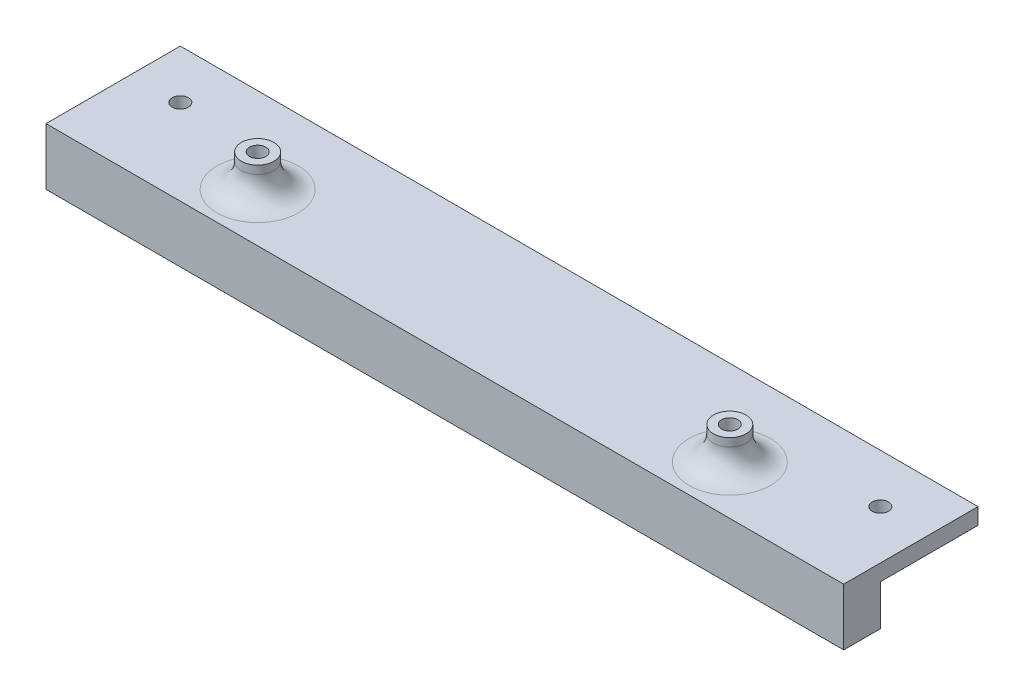
SolidWorks part; units mm, degrees
ref_plane "前视基准面" through (0, 0, 0) normal (0, 0, 1) x (1, 0, 0)
ref_plane "上视基准面" through (0, 0, 0) normal (0, 1, 0) x (1, 0, 0)
ref_plane "右视基准面" through (0, 0, 0) normal (1, 0, 0) x (0, 0, -1)
sketch "草图1" plane through (0, 0, 0) normal (0, 1, 0) x (1, 0, 0)
  line L0 (130, 16.5685) -> (106.5685, 40) construction
  line L2 (16.5685, 40) -> (-16.5685, 40) construction
  line L3 (-16.5685, 40) -> (-40, 16.5685) construction
  line L4 (-40, 16.5685) -> (-40, -16.5685) construction
  line L5 (-40, -16.5685) -> (-16.5685, -40) construction
  line L6 (-16.5685, -40) -> (16.5685, -40) construction
  line L9 (106.5685, 40) -> (73.4315, 40) construction
  line L13 (73.4315, -40) -> (106.5685, -40) construction
  line L14 (106.5685, -40) -> (130, -16.5685) construction
  line L15 (130, -16.5685) -> (130, 16.5685) construction
  line L16 (0, 0) -> (90, 0) construction
  line L17 (16.5685, 40) -> (73.4315, 40) construction
  line L18 (16.5685, -40) -> (73.4315, -40) construction
  line L19 (16.5685, 42.5) -> (73.4315, 42.5)
  line L20 (16.5685, 42.5) -> (-17.6041, 42.5)
  line L21 (-17.6041, 42.5) -> (-42.5, 17.6041)
  line L22 (-42.5, 17.6041) -> (-42.5, -17.6041)
  line L23 (-42.5, -17.6041) -> (-17.6041, -42.5)
  line L24 (-17.6041, -42.5) -> (16.5685, -42.5)
  line L25 (73.4315, -42.5) -> (107.6041, -42.5)
  line L26 (107.6041, -42.5) -> (132.5, -17.6041)
  line L27 (132.5, -17.6041) -> (132.5, 17.6041)
  line L28 (132.5, 17.6041) -> (107.6041, 42.5)
  line L29 (107.6041, 42.5) -> (73.4315, 42.5)
  line L30 (16.5685, -42.5) -> (73.4315, -42.5)
  line L31 (28.2843, 28.2843) -> (16.5685, 40)
  line L32 (40, -16.5685) -> (40, 0)
  line L33 (16.5685, -40) -> (28.2843, -28.2843)
  line L34 (16.5685, 37.5) -> (-15.533, 37.5)
  line L41 (-15.533, 37.5) -> (-37.5, 15.533)
  line L42 (-37.5, 15.533) -> (-37.5, -15.533)
  line L43 (-37.5, -15.533) -> (-15.533, -37.5)
  line L44 (-15.533, -37.5) -> (-7.5, -37.5)
  line L45 (16.5685, -37.5) -> (73.4315, -37.5)
  line L46 (73.4315, -37.5) -> (83.1419, -37.5)
  line L47 (105.533, -37.5) -> (127.5, -15.533)
  line L48 (127.5, -15.533) -> (127.5, 15.533)
  line L49 (127.5, 15.533) -> (105.533, 37.5)
  line L50 (105.533, 37.5) -> (73.4315, 37.5)
  line L51 (16.5685, 37.5) -> (73.4315, 37.5)
  line L52 (-7.5, 24) -> (-29.033, 24)
  line L53 (-1, -36) -> (91, -36) construction
  line L54 (-1, -28) -> (-1, 16) construction
  line L55 (7, 24) -> (83, 24)
  line L56 (91, -28) -> (91, 16) construction
  line L57 (-1, -36) -> (91, 24) construction
  line L58 (-1, 24) -> (91, -36) construction
  line L59 (97.5, 24) -> (119.033, 24)
  line L60 (-7.5, 24) -> (-7.5, -37.5)
  line L61 (91, 16) -> (91, -28)
  line L62 (6.8581, -37.5) -> (16.5685, -37.5)
  line L63 (-15.533, -37.5) -> (16.5685, -37.5) construction
  line L64 (-1, -28) -> (-1, 16)
  line L65 (97.5, 24) -> (97.5, -37.5)
  line L66 (97.5, -37.5) -> (105.533, -37.5)
  line L67 (73.4315, -37.5) -> (105.533, -37.5) construction
  arc A0 (0, 40) -> (0, -40) centre (0, 0) ccw construction
  arc A1 (90, -40) -> (90, 40) centre (90, 0) ccw construction
  arc A2 (-1, 16) -> (7, 24) centre (-1, 24) ccw
  arc A3 (83, 24) -> (91, 16) centre (91, 24) ccw
  arc A5 (6.8581, -37.5) -> (-1, -28) centre (-1, -36) ccw
  arc A7 (97.7672, -40.2667) -> (98.1083, -39.6704) centre (91, -36) ccw
  arc A9 (91, -28) -> (83.1419, -37.5) centre (91, -36) ccw
  point P2 (45, 0)
  point P20 (45, -6)
  dimension "D1" = 80
  dimension "D2" = 80
  dimension "D12" = 4
  dimension "D13" = 16
  dimension "D17" = 135
  dimension "D18" = 8
  dimension "D3" = 90
  dimension "D4" = 56.8629
  dimension "D5" = 56.8629
  dimension "D8" = 60
  dimension "D9" = 92
  dimension "D15" = 37.5
  dimension "D6" = 2.5
  dimension "D7" = 2.5
  dimension "D10" = 5
  dimension "D11" = 5
  dimension "D14" = 2
  dimension "D16" = 2
ref_plane "基准面2" through (0, 10, 0) normal (0, 1, 0) x (1, 0, 0)
sketch "草图10" plane through (0, 10, 0) normal (0, 1, 0) x (1, 0, 0)
  line L0 (-4, 29.5) -> (-4, 12.9995)
  line L6 (94, 29.5) -> (94, 12.9995)
  line L7 (-4, 29.5) -> (94, 29.5)
  line L20 (-4, 12.9995) -> (94, 12.9995)
  line L21 (-4, 17.5) -> (8, 17.5)
  line L22 (8, 17.5) -> (8, 29.5)
  line L23 (94, 17.5) -> (82, 17.5)
  line L24 (82, 17.5) -> (82, 29.5)
  circle A0 centre (2, 23.5) radius 1
  circle A1 centre (88, 23.5) radius 1
  circle A4 centre (16.0034, 18.9995) radius 1
  circle A5 centre (74.0034, 18.9995) radius 1
  circle A8 centre (16.0034, -30.0005) radius 1 [skipped]
  circle A9 centre (74.0034, -30.0005) radius 1 [skipped]
  circle A10 centre (2, -34.5) radius 1 [skipped]
  circle A11 centre (88, -34.5) radius 1 [skipped]
  circle A12 centre (16.0034, 18.9995) radius 2
  circle A13 centre (74.0034, 18.9995) radius 2
  circle A14 centre (16.0034, 18.9995) radius 4
  circle A15 centre (74.0034, 18.9995) radius 4
  point P12 (45, 23.5)
  point P13 (45, -34.5)
  point P22 (74.0034, -5.5005)
  point P25 (16.0034, -5.5005)
  dimension "D2" = 2
  dimension "D7" = 2
  dimension "D5" = 2
  dimension "D1" = 2
  dimension "D3" = 2
  dimension "D4" = 2
  dimension "D8" = 2
extrude "凸台-拉伸5" add sketch "草图10" against normal blind 5 contours L23 L24 L7 L22 L21 L0 L20 L6 A5 A4 | A14 A12 | A12 A4 | A15 A13 | A13 A5 region at (44.9997, 10, -20.9063) region at (14.06, 10, -18.9995) region at (72.06, 10, -18.9995) region at (12.1165, 10, -18.9995) region at (70.1165, 10, -18.9995)
extrude "凸台-拉伸6" add sketch "草图10<4>" along normal blind 2 contours L21 L22 L7 L0 A0 | L23 L24 L7 L22 L21 L0 L20 L6 A5 A4 | L24 L23 L6 L7 A1 | A14 A12 | A12 A4 | A15 A13 | A13 A5 region at (2, 10, -29.3303) region at (44.9997, 10, -20.9063) region at (88, 10, -29.3303) region at (14.06, 10, -18.9995) region at (72.06, 10, -18.9995) region at (12.1165, 10, -18.9995) region at (70.1165, 10, -18.9995)
sketch "草图10<4>" plane through (0, 10, 0) normal (0, 1, 0) x (1, 0, 0) same geometry as "草图10"
sketch "草图11" plane through (0, 12, 0) normal (0, 1, 0) x (1, 0, 0)
  circle A0 centre (16.0034, 18.9995) radius 2
  circle A1 centre (16.0034, 18.9995) radius 4
  circle A2 centre (74.0034, 18.9995) radius 4
  circle A3 centre (74.0034, 18.9995) radius 2
  circle A4 centre (16.0034, 18.9995) radius 1
  circle M9 centre (16.0034, 18.9995) radius 1
  circle M10 centre (74.0034, 18.9995) radius 1
  dimension "D1" = 2
extrude "凸台-拉伸8" add sketch "草图11" along normal blind 4 contours A0 M9 | A3 M10 region at (14.06, 12, -18.9995) region at (72.06, 12, -18.9995)
fillet "圆角30" radius 3 2 edges at (16.0034, 12, -16.9995) (74.0034, 12, -16.9995)
